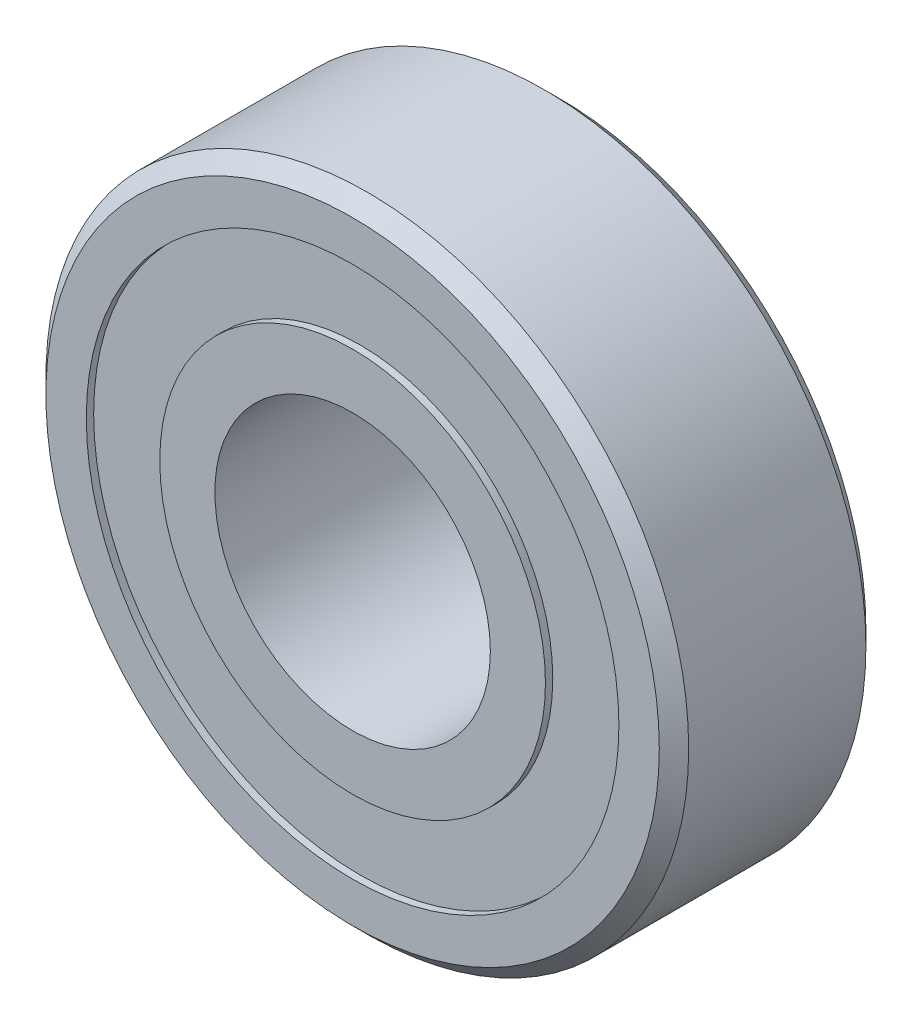
SolidWorks part; units mm, degrees
ref_plane "Front Plane" through (0, 0, 0) normal (0, 0, 1) x (1, 0, 0)
ref_plane "Top Plane" through (0, 0, 0) normal (0, 1, 0) x (1, 0, 0)
ref_plane "Right Plane" through (0, 0, 0) normal (1, 0, 0) x (0, 0, -1)
sketch "Sketch1" plane through (0, 0, 0) normal (0, 0, 1) x (1, 0, 0)
  circle A0 centre (0, 0) radius 11.1125
  dimension "D1" = 22.225
extrude "Boss-Extrude1" add sketch "Sketch1" along normal blind 7.1437
chamfer "Chamfer1" distance 0.508 angle 45 2 edges at (11.1125, 0, 0) (11.1125, 0, 7.1437)
hole_wizard "3/8 (0.375) Diameter Hole1" positions "Sketch2" profile "Sketch4" hole size "3/8" standard "ANSI Inch" end condition through all
sketch "Sketch2" plane through (0, 0, 7.1437) normal (0, 0, 1) x (1, 0, 0)
  point P0 (0, 0)
sketch "Sketch4" plane through (0, 0, 7.1437) normal (1, 0, 0) x (0, -1, 0)
  line L0 (0, 0) -> (0, 7.1438)
  line L1 (0, 7.1438) -> (4.7625, 7.1438)
  line L2 (4.7625, 7.1438) -> (4.7625, 0)
  line L5 (4.7625, 0) -> (0, 0)
  line L11 (0, -6.35) -> (0, 107.95) construction
  dimension "Thru Hole Dia." = 9.525
  dimension "Thru Hole Depth" = 7.1437
sketch "Sketch5" plane through (0, 0, 7.1437) normal (0, 0, 1) x (1, 0, 0)
  circle A0 centre (0, 0) radius 7.9375 construction
  circle A1 centre (0, 0) radius 9.2075
  circle A2 centre (0, 0) radius 6.6675
  dimension "D1" = 15.875
  dimension "D2" = 1.27
  dimension "D3" = 1.27
extrude "Cut-Extrude1" cut sketch "Sketch5" against normal blind 0.254
sketch "Sketch6" plane through (0, 0, 0) normal (0, 0, -1) x (-1, 0, 0)
  circle A0 centre (0, 0) radius 7.9375 construction
  circle A1 centre (0, 0) radius 9.2075
  circle A2 centre (0, 0) radius 6.6675
  dimension "D1" = 15.875
  dimension "D2" = 1.27
  dimension "D3" = 1.27
extrude "Cut-Extrude2" cut sketch "Sketch6" against normal blind 0.254
